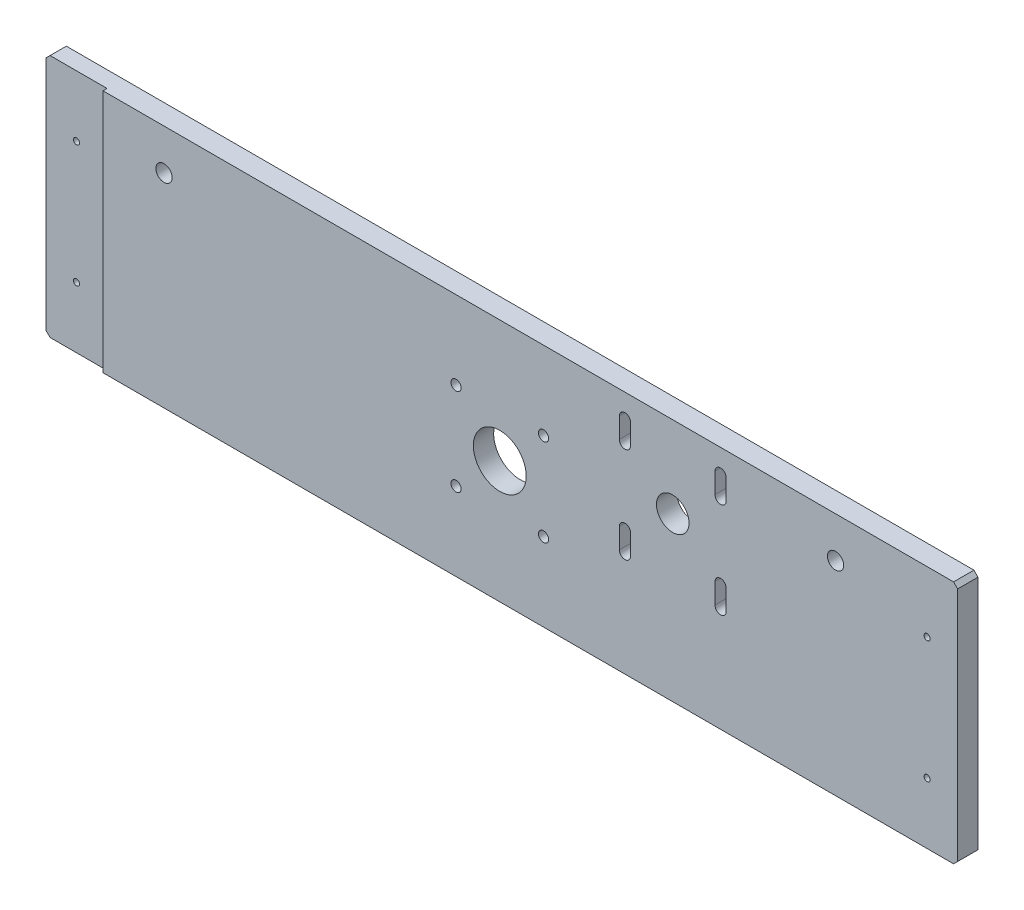
SolidWorks part; units mm, degrees
ref_plane "Piano frontale" through (0, 0, 0) normal (0, 0, 1) x (1, 0, 0)
ref_plane "Piano superiore" through (0, 0, 0) normal (0, 1, 0) x (1, 0, 0)
ref_plane "Piano destro" through (0, 0, 0) normal (1, 0, 0) x (0, 0, -1)
sketch "Schizzo1" plane through (0, 0, 0) normal (0, 0, 1) x (1, 0, 0)
  line L0 (225, 120) -> (225, 0) construction
  line L1 (2, 0) -> (448, 0)
  line L2 (0, 2) -> (0, 118)
  line L3 (2, 120) -> (448, 120)
  line L4 (450, 2) -> (450, 118)
  line L5 (203.5, 52.7163) -> (203.5, 5.9855) construction
  line L6 (250.0723, 81.5) -> (199.9971, 81.5) construction
  line L7 (225, 60) -> (243.5099, 60) construction
  line L8 (459.2931, 100) -> (370.8276, 100) construction
  line L21 (0, 118) -> (2, 120)
  line L22 (2, 0) -> (0, 2)
  line L23 (448, 0) -> (450, 2)
  line L24 (448, 120) -> (450, 118)
  line L25 (225, 60) -> (450, 60) construction
  line L26 (344.754, 80) -> (282.8483, 80) construction
  line L27 (333.5, 108.5) -> (333.5, 98.5) construction
  line L28 (330.75, 108.5) -> (330.75, 98.5)
  line L29 (336.25, 108.5) -> (336.25, 98.5)
  line L30 (286.5, 108.5) -> (286.5, 98.5) construction
  line L31 (289.25, 108.5) -> (289.25, 98.5)
  line L32 (283.75, 108.5) -> (283.75, 98.5)
  line L33 (333.5, 51.5) -> (333.5, 61.5) construction
  line L34 (330.75, 51.5) -> (330.75, 61.5)
  line L35 (336.25, 51.5) -> (336.25, 61.5)
  line L36 (286.5, 51.5) -> (286.5, 61.5) construction
  line L37 (289.25, 51.5) -> (289.25, 61.5)
  line L38 (283.75, 51.5) -> (283.75, 61.5)
  line L42 (310, 120) -> (310, 0) construction
  circle A0 centre (225, 60) radius 13
  circle A3 centre (390, 100) radius 4
  circle A10 centre (60, 100) radius 4
  circle A11 centre (15, 30) radius 1.5
  circle A12 centre (435, 30) radius 1.5
  circle A13 centre (203.5, 81.5) radius 2.5
  circle A14 centre (246.5, 81.5) radius 2.5
  circle A15 centre (246.5, 38.5) radius 2.5
  circle A16 centre (203.5, 38.5) radius 2.5
  circle A17 centre (435, 90) radius 1.5
  circle A18 centre (15, 90) radius 1.5
  arc A19 (330.75, 108.5) -> (336.25, 108.5) centre (333.5, 108.5) cw
  arc A20 (336.25, 98.5) -> (330.75, 98.5) centre (333.5, 98.5) cw
  arc A21 (289.25, 108.5) -> (283.75, 108.5) centre (286.5, 108.5) ccw
  arc A22 (283.75, 98.5) -> (289.25, 98.5) centre (286.5, 98.5) ccw
  arc A23 (330.75, 51.5) -> (336.25, 51.5) centre (333.5, 51.5) ccw
  arc A24 (336.25, 61.5) -> (330.75, 61.5) centre (333.5, 61.5) ccw
  arc A25 (289.25, 51.5) -> (283.75, 51.5) centre (286.5, 51.5) cw
  arc A26 (283.75, 61.5) -> (289.25, 61.5) centre (286.5, 61.5) cw
  circle A27 centre (310, 80) radius 8
  point P0 (0, 0)
  point P1 (450, 120)
  point P2 (0, 120)
  point P3 (450, 0)
  point P13 (203.5, 81.5)
  point P14 (246.5, 81.5)
  point P15 (203.5, 38.5)
  point P17 (246.5, 38.5)
  point P80 (310, 80)
  point P83 (333.5, 103.5)
  point P90 (286.5, 103.5)
  point P97 (333.5, 56.5)
  point P104 (286.5, 56.5)
  dimension "D4" = 26
  dimension "D10" = 8
  dimension "D15" = 3
  dimension "D17" = 5
  dimension "D25" = 16
  dimension "D1" = 120
  dimension "D2" = 450
  dimension "D3" = 60
  dimension "D5" = 21.5
  dimension "D6" = 21.5
  dimension "D7" = 20
  dimension "D12" = 60
  dimension "D14" = 30
  dimension "D16" = 15
  dimension "D18" = 40
  dimension "D23" = 23.5
  dimension "D24" = 23.5
  dimension "D26" = 5.5
  dimension "D27" = 10
  dimension "D29" = 140
extrude "Estrusione-Estrusione1" add sketch "Schizzo1" against normal blind 10
sketch "Schizzo2" plane through (0, 0, 0) normal (0, 0, 1) x (1, 0, 0)
  line L0 (448, 120) -> (2, 120) construction
  line L1 (30, 120) -> (0, 120)
  line L2 (30, 120) -> (30, 0)
  line L3 (30, 0) -> (0, 0)
  line L4 (0, 120) -> (0, 0)
  line L5 (315.2194, 120) -> (315.2194, -23.5993) construction
  line L6 (630.4389, 120) -> (630.4389, 0)
  line L7 (600.4389, 0) -> (630.4389, 0)
  line L8 (600.4389, 120) -> (600.4389, 0)
  line L9 (600.4389, 120) -> (630.4389, 120)
  dimension "D1" = 30
extrude "Taglio-Estrusione1" cut sketch "Schizzo2" against normal blind 2
